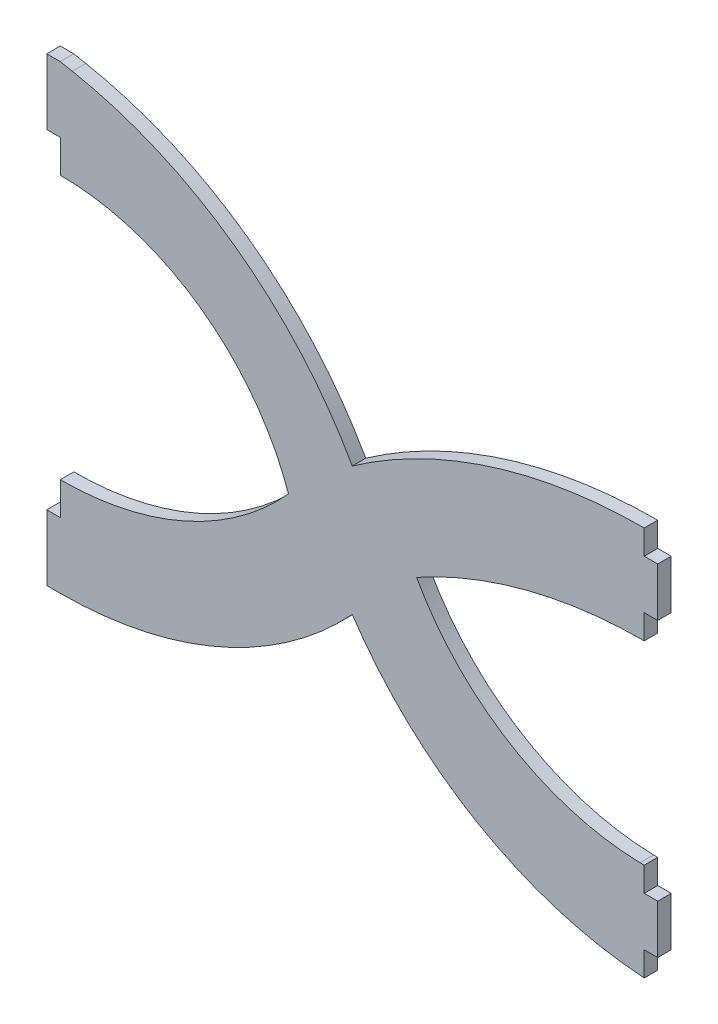
SolidWorks part; units mm, degrees
ref_plane "Front Plane" through (0, 0, 0) normal (0, 0, 1) x (1, 0, 0)
ref_plane "Top Plane" through (0, 0, 0) normal (0, 1, 0) x (1, 0, 0)
ref_plane "Right Plane" through (0, 0, 0) normal (1, 0, 0) x (0, 0, -1)
sketch "Sketch1" plane through (0, 0, 0) normal (0, 0, 1) x (1, 0, 0)
  line L1 (-141.9798, 90.4351) -> (99.3202, 90.4351)
  line L2 (-141.9798, 90.4351) -> (-141.9798, -107.6849)
  line L3 (-141.9798, -107.6849) -> (99.3202, -107.6849)
  line L4 (99.3202, 90.4351) -> (99.3202, -107.6849)
  dimension "D1" = 241.3
  dimension "D2" = 198.12
extrude "Boss-Extrude1" add sketch "Sketch1" along normal blind 5.334
sketch "Sketch2" plane through (0, 0, 5.334) normal (0, 0, 1) x (1, 0, 0)
  line L0 (99.3202, -107.6849) -> (99.3202, 90.4351) construction
  line L1 (99.3202, -107.6849) -> (93.9862, -107.6849)
  line L2 (99.3202, -107.6849) -> (99.3202, -98.0329)
  line L3 (99.3202, -98.0329) -> (93.9862, -98.0329)
  line L4 (93.9862, -107.6849) -> (93.9862, -98.0329)
  line L5 (99.3202, -78.7289) -> (93.9862, -78.7289)
  line L7 (93.9862, 17.2831) -> (99.3202, 17.2831)
  line L8 (93.9862, 17.2831) -> (93.9862, -78.7289)
  line L9 (93.9862, 36.5871) -> (93.9862, 17.2831) construction
  line L10 (99.3202, 90.4351) -> (93.9862, 90.4351)
  line L11 (99.3202, 90.4351) -> (99.3202, 36.5871)
  line L12 (99.3202, 36.5871) -> (93.9862, 36.5871)
  line L13 (93.9862, 90.4351) -> (93.9862, 36.5871)
  line L16 (99.3202, 17.2831) -> (99.3202, -78.7289)
  line L18 (93.9862, -78.7289) -> (93.9862, -98.0329) construction
  dimension "D1" = 5.334
  dimension "D3" = 19.304
  dimension "D4" = 9.652
  dimension "D5" = 19.304
  dimension "D2" = 96.012
extrude "Cut-Extrude1" cut sketch "Sketch2" against normal through all
sketch "Sketch3" plane through (0, 0, 5.334) normal (0, 0, 1) x (1, 0, 0)
  line L1 (-141.9798, -107.6849) -> (-136.6458, -107.6849)
  line L2 (-141.9798, -107.6849) -> (-141.9798, -91.4289)
  line L3 (-141.9798, -91.4289) -> (-136.6458, -91.4289)
  line L4 (-136.6458, -107.6849) -> (-136.6458, -91.4289)
  line L5 (-141.9798, 90.4351) -> (-141.9798, -107.6849) construction
  line L6 (-136.6458, -65.5209) -> (-141.9798, -65.5209)
  line L7 (-136.6458, -65.5209) -> (-136.6458, 64.5271)
  line L8 (-136.6458, 64.5271) -> (-141.9798, 64.5271)
  line L9 (-141.9798, -65.5209) -> (-141.9798, 64.5271)
  line L10 (-136.6458, -65.5209) -> (-136.6458, -91.4289) construction
  line L11 (-136.6458, 64.5271) -> (-136.6458, 90.4351) construction
  line L12 (93.9862, 90.4351) -> (-141.9798, 90.4351) construction
  dimension "D1" = 16.256
  dimension "D2" = 25.908
  dimension "D3" = 25.908
  dimension "D4" = 5.334
extrude "Cut-Extrude2" cut sketch "Sketch3" against normal through all
sketch "Sketch5" plane through (0, 0, 5.334) normal (0, 0, 1) x (1, 0, 0)
  line L0 (-136.6458, -91.4289) -> (93.9862, -107.6849) construction
  line L1 (-136.6458, -91.4289) -> (93.9862, -107.6849)
  line L2 (-136.6458, -91.4289) -> (-136.6458, -146.6044)
  line L3 (93.9862, -107.6849) -> (93.9862, -162.8604)
  line L4 (-136.6458, -146.6044) -> (93.9862, -162.8604)
extrude "Cut-Extrude5" cut sketch "Sketch5" against normal through all
sketch "Sketch6" plane through (0, 0, 5.334) normal (0, 0, 1) x (1, 0, 0)
  line L0 (-136.6458, 64.5271) -> (-136.6458, 90.4351) construction
  line L1 (93.9862, 90.4351) -> (-141.9798, 90.4351) construction
  line L2 (93.9862, 36.5871) -> (93.9862, 46.2391) construction
  line L3 (93.9862, 90.4351) -> (93.9862, 36.5871) construction
  line L4 (-136.6458, 90.4351) -> (93.9862, 46.2391)
  line L5 (-136.6458, 90.4351) -> (-136.6458, 134.6311)
  line L6 (93.9862, 46.2391) -> (93.9862, 90.4351)
  line L7 (-136.6458, 134.6311) -> (93.9862, 90.4351)
  dimension "D1" = 9.652
extrude "Cut-Extrude6" cut sketch "Sketch6" against normal through all
sketch "Sketch7" plane through (0, 0, 5.334) normal (0, 0, 1) x (1, 0, 0)
  line L0 (-21.3298, 68.3371) -> (-21.3298, -99.5569) construction
  line L1 (-136.6458, 90.4351) -> (93.9862, 46.2391) construction
  line L2 (93.9862, -107.6849) -> (-136.6458, -91.4289) construction
  line L3 (93.9862, -30.7229) -> (-136.6458, -0.4969) construction
  line L4 (93.9862, 17.2831) -> (93.9862, -78.7289) construction
  line L5 (-136.6458, -65.5209) -> (-136.6458, 64.5271) construction
  line L6 (-136.6458, 64.5271) -> (-136.6458, 51.5731) construction
  line L7 (-136.6458, -65.5209) -> (-136.6458, -52.5669) construction
  line L8 (93.9862, 17.2831) -> (93.9862, 7.6311) construction
  line L9 (93.9862, -78.7289) -> (93.9862, -69.0769) construction
  line L10 (-136.6458, 64.5271) -> (-131.8569, 89.5174) construction
  line L11 (93.9862, 36.5871) -> (93.9862, 46.2391) construction
  line L12 (-131.8569, 89.5174) -> (93.9862, 46.2391)
  line L13 (-136.6458, -65.5209) -> (-136.6458, -91.4289) construction
  line L14 (93.9862, -98.0329) -> (93.3092, -107.6372) construction
  line L15 (-136.6458, -91.4289) -> (93.3092, -107.6372)
  circle A0 centre (-21.3298, -15.6099) radius 25.4 construction
  arc A1 (93.9862, 7.6311) -> (4.0702, -15.6099) centre (93.9862, -177.9253) ccw
  arc A2 (4.0702, -15.6099) -> (92.3478, -69.0769) centre (94.8631, 34.6856) ccw
  arc A3 (92.3478, -69.0769) -> (93.9862, 7.6311) centre (93.2775, -30.7253) ccw
  arc A4 (-136.6458, 51.5731) -> (-46.5144, -12.3093) centre (-136.6458, -43.9511) cw
  arc A5 (-136.6458, -52.5669) -> (-46.5144, -12.3093) centre (-136.6458, 68.4578) ccw
  arc A6 (-136.6458, 51.5731) -> (-136.6458, -52.5669) centre (-136.6458, -0.4969) ccw
  arc A7 (-131.8569, 89.5174) -> (-21.3298, 9.7901) centre (-162.252, -69.0961) cw
  arc A8 (93.9862, 46.2391) -> (-21.3298, 9.7901) centre (93.9862, -154.4017) ccw
  arc A9 (-136.6458, -91.4289) -> (-21.3298, -41.0099) centre (-136.6458, 65.6533) ccw
  arc A10 (93.3092, -107.6372) -> (-21.3298, -41.0099) centre (103.8923, 42.5097) cw
extrude "Cut-Extrude7" cut sketch "Sketch7" against normal through all
equation "\"MDF\"= .21in"
equation "\"Foamcore\"= .13in"
equation "\"Gmaterial\"= \"MDF\""
equation "\"D1@Boss-Extrude1\"=\"MDF\""
equation "\"D1@Sketch2\"=\"MDF\""
equation "\"D4@Sketch3\"=\"MDF\""
